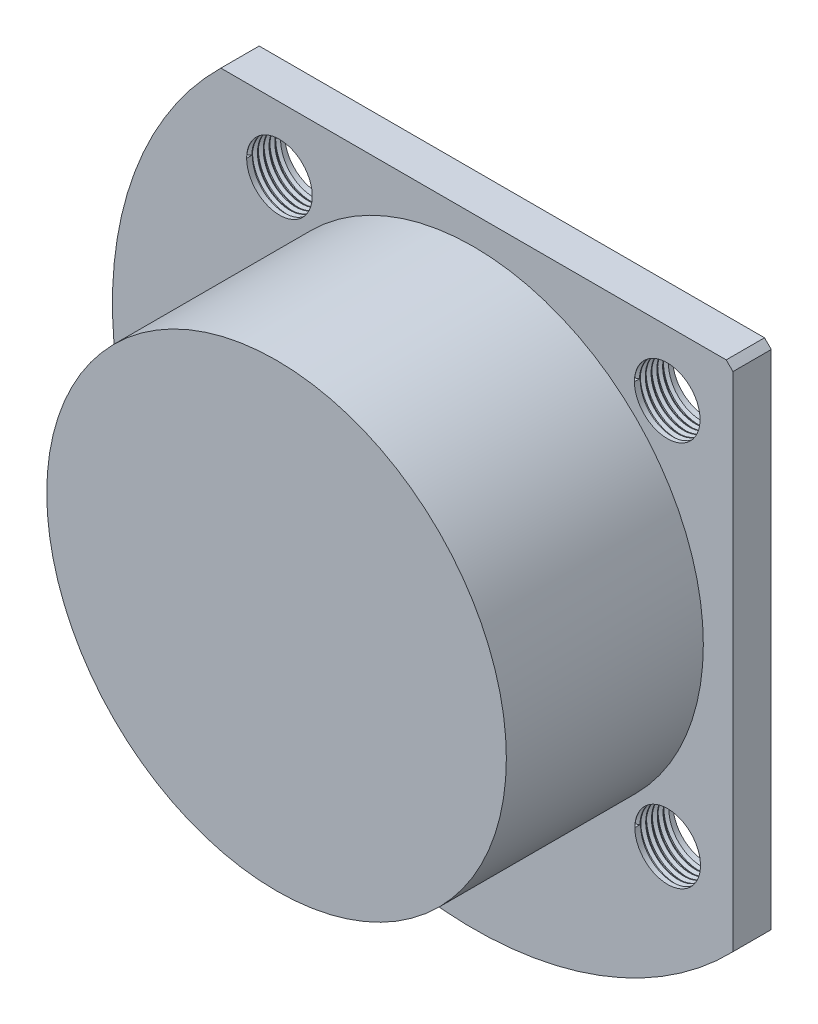
SolidWorks part; units mm, degrees
ref_plane "Front Plane" through (0, 0, 0) normal (0, 0, 1) x (1, 0, 0)
ref_plane "Top Plane" through (0, 0, 0) normal (0, 1, 0) x (1, 0, 0)
ref_plane "Right Plane" through (0, 0, 0) normal (1, 0, 0) x (0, 0, -1)
sketch "Sketch1" plane through (0, 0, 0) normal (0, 0, 1) x (1, 0, 0)
  circle A0 centre (0, 0) radius 33
  dimension "D1" = 66
extrude "Boss-Extrude1" add sketch "Sketch1" along normal blind 21.5
sketch "Sketch2" plane through (0, 0, 21.5) normal (0, 0, 1) x (1, 0, 0)
  circle A0 centre (0, 0) radius 21
  dimension "D1" = 42
extrude "Cut-Extrude1" cut sketch "Sketch2" against normal blind 18 flip side to cut
sketch "Sketch3" plane through (0, 0, 0) normal (0, 0, -1) x (-1, 0, 0)
  circle A0 centre (0, 0) radius 19
  dimension "D1" = 38
extrude "Cut-Extrude2" cut sketch "Sketch3" against normal blind 18
hole_wizard "Ø6.0mm Dowel Hole1" positions "3DSketch3" profile "Sketch8" hole size "Ø6.0" standard "ISO" end condition through all
sketch3d "3DSketch3"
  point P0 (17.7023, 17.653, 0)
  point P2 (-17.6128, -17.7423, 0)
  point P4 (-17.7347, 17.6204, 0)
  point P6 (17.7413, -17.6138, 0)
  dimension "D1" = 25
  dimension "D2" = 25
  dimension "D3" = 25
  dimension "D4" = 25
sketch "Sketch8" plane through (17.7023, 17.653, 0) normal (1, 0, 0) x (0, 1, 0)
  line L0 (0, 0) -> (0, 21.5)
  line L1 (0, 21.5) -> (3, 21.5)
  line L2 (3, 21.5) -> (3, 0)
  line L5 (3, 0) -> (0, 0)
  line L11 (0, -6.35) -> (0, 107.95) construction
  dimension "Thru Hole Dia." = 6
  dimension "Thru Hole Depth" = 21.5
sketch "Sketch9" plane through (0, 0, 0) normal (0, 0, -1) x (-1, 0, 0)
  line L0 (-23.09, 23.5765) -> (23.09, 23.5765)
  circle A0 centre (0, 0) radius 33 construction
extrude "Cut-Extrude3" cut sketch "Sketch9" against normal blind 18 and the other way through all
sketch "Sketch10" plane through (0, 0, 0) normal (0, 0, -1) x (-1, 0, 0)
  line L0 (-23.7061, 22.957) -> (-23.7061, -22.957)
  arc A0 (-23.09, 23.5765) -> (23.09, 23.5765) centre (0, 0) ccw construction
extrude "Cut-Extrude4" cut sketch "Sketch10" against normal blind 18 and the other way through all flip side to cut
thread "螺纹线1" pitch 0.5292 method cut profile "螺纹线轮廓1" start angle 0, offset 0, length 2.7, pitch 0.5292, diameter 6
ref_plane "基准面1" through (-20.7347, 17.6204, 3.5) normal (0, 1, 0) x (1, 0, 0)
sketch "螺纹线轮廓1" plane through (-20.7347, 17.6204, 3.5) normal (0, 1, 0) x (1, 0, 0)
  line L0 (0, 0) -> (0, 0.5292) construction
  line L11 (0, 0) -> (0, 0.463)
  line L12 (0, 0.463) -> (-0.2864, 0.2977)
  line L13 (-0.2864, 0.2977) -> (-0.2864, 0.1654)
  line L15 (-0.2864, 0.1654) -> (0, 0)
  line L17 (-0.2864, 0.2315) -> (0, 0.2315) construction
  point P2 (0, 0)
  dimension "Pitch" = 0.5292
  dimension "Profile_Angle" = 60
  dimension "Profile_Land" = 0.1323
  dimension "Profile_Height" = 0.2864
thread "螺纹线2" pitch 0.5292 method cut profile "螺纹线轮廓2" start angle 0, offset 0, length 2.7, pitch 0.5292, diameter 6
ref_plane "基准面2" through (14.7023, 17.653, 3.5) normal (0, 1, 0) x (1, 0, 0)
sketch "螺纹线轮廓2" plane through (14.7023, 17.653, 3.5) normal (0, 1, 0) x (1, 0, 0)
  line L0 (0, 0) -> (0, 0.5292) construction
  line L11 (0, 0) -> (0, 0.463)
  line L12 (0, 0.463) -> (-0.2864, 0.2977)
  line L13 (-0.2864, 0.2977) -> (-0.2864, 0.1654)
  line L15 (-0.2864, 0.1654) -> (0, 0)
  line L17 (-0.2864, 0.2315) -> (0, 0.2315) construction
  point P2 (0, 0)
  dimension "Pitch" = 0.5292
  dimension "Profile_Angle" = 60
  dimension "Profile_Land" = 0.1323
  dimension "Profile_Height" = 0.2864
thread "螺纹线3" pitch 0.5292 method cut profile "螺纹线轮廓3" start angle 0, offset 0, length 2.7, pitch 0.5292, diameter 6
ref_plane "基准面3" through (14.7413, -17.6138, 3.5) normal (0, 1, 0) x (1, 0, 0)
sketch "螺纹线轮廓3" plane through (14.7413, -17.6138, 3.5) normal (0, 1, 0) x (1, 0, 0)
  line L0 (0, 0) -> (0, 0.5292) construction
  line L11 (0, 0) -> (0, 0.463)
  line L12 (0, 0.463) -> (-0.2864, 0.2977)
  line L13 (-0.2864, 0.2977) -> (-0.2864, 0.1654)
  line L15 (-0.2864, 0.1654) -> (0, 0)
  line L17 (-0.2864, 0.2315) -> (0, 0.2315) construction
  point P2 (0, 0)
  dimension "Pitch" = 0.5292
  dimension "Profile_Angle" = 60
  dimension "Profile_Land" = 0.1323
  dimension "Profile_Height" = 0.2864
thread "螺纹线4" pitch 0.5292 method cut profile "螺纹线轮廓4" start angle 0, offset 0, length 2.7, pitch 0.5292, diameter 6
ref_plane "基准面4" through (-20.6128, -17.7423, 3.5) normal (0, 1, 0) x (1, 0, 0)
sketch "螺纹线轮廓4" plane through (-20.6128, -17.7423, 3.5) normal (0, 1, 0) x (1, 0, 0)
  line L0 (0, 0) -> (0, 0.5292) construction
  line L11 (0, 0) -> (0, 0.463)
  line L12 (0, 0.463) -> (-0.2864, 0.2977)
  line L13 (-0.2864, 0.2977) -> (-0.2864, 0.1654)
  line L15 (-0.2864, 0.1654) -> (0, 0)
  line L17 (-0.2864, 0.2315) -> (0, 0.2315) construction
  point P2 (0, 0)
  dimension "Pitch" = 0.5292
  dimension "Profile_Angle" = 60
  dimension "Profile_Land" = 0.1323
  dimension "Profile_Height" = 0.2864
